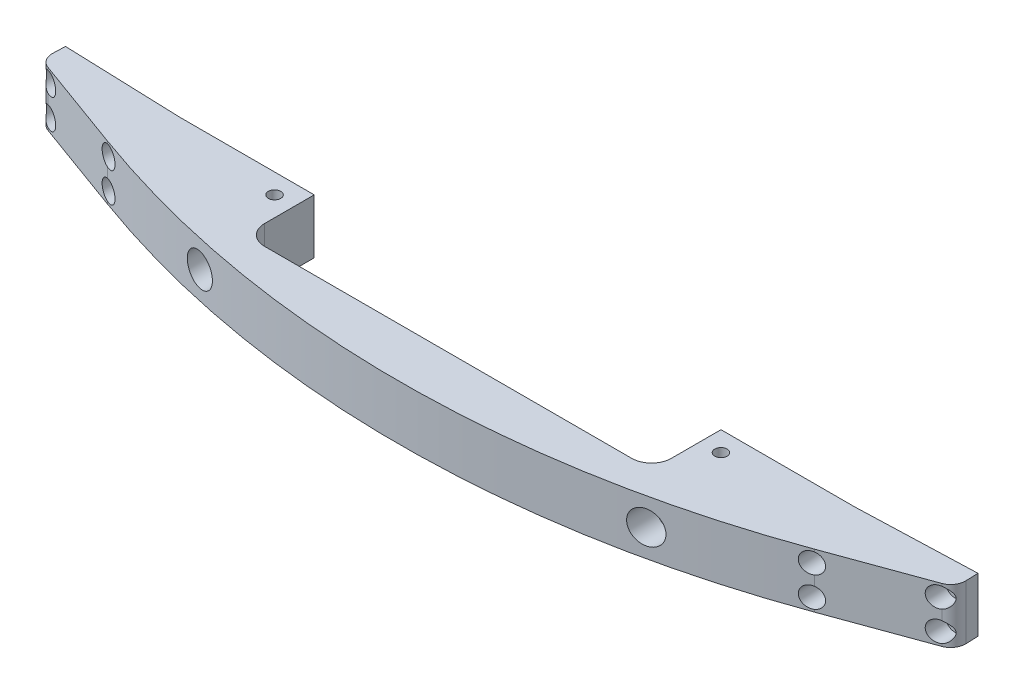
SolidWorks part; units mm, degrees
material "2014-T6"
ref_plane "Ebene vorne" through (0, 0, 0) normal (0, 0, 1) x (1, 0, 0)
ref_plane "Ebene oben" through (0, 0, 0) normal (0, 1, 0) x (1, 0, 0)
ref_plane "Ebene rechts" through (0, 0, 0) normal (1, 0, 0) x (0, 0, -1)
sketch "Skizze1" plane through (0, 0, 0) normal (0, 1, 0) x (1, 0, 0)
  line L0 (0, 87.9519) -> (0, -34.7709) construction
  line L1 (80, 0) -> (-80, 0) construction
  line L2 (-80, 4) -> (-45, 4)
  line L3 (-81.3681, -3.7588) -> (-71.2753, -7.4322)
  line L4 (0, -20) -> (0, -10)
  line L5 (-41, -10) -> (0, -10)
  line L6 (-41, 4) -> (-41, -10)
  line L7 (-80, 4) -> (-91.9927, 4.4188)
  line L8 (-45, 4) -> (-41, 4)
  line L9 (-92.1413, 0.1624) -> (-91.9781, 4.8376)
  line L10 (-92.1413, 0.1624) -> (-81.3681, -3.7588)
  line L11 (-91.9781, 4.8376) -> (-67.9927, 4)
  line L12 (-80, 4) -> (-79.9854, 4.4188) construction
  arc A0 (-80, 4) -> (-81.3681, -3.7588) centre (-80, 0) ccw construction
  arc A1 (-71.2753, -7.4322) -> (0, -20) centre (0, 188.395) ccw
  dimension "D2" = 160
  dimension "D9" = 20
  dimension "D3" = 8
  dimension "D7" = 2
  dimension "D1" = 12
  dimension "D4" = 90
  dimension "D5" = 20
  dimension "D6" = 4
  dimension "D8" = 10
extrude "Aufsatz-Linear austragen1" add sketch "Skizze1" along normal mid plane 11 contours A0 | L3 A1 L4 L5 L6 A0 | L7 L12 L11 L9 | L12 L2 L11 region at (-82.6569, 0, -4.3257) region at (-46.1863, 0, 7.1587)
fillet "Verrundung1" radius 4 1 edges at (-41, 0, 10)
hole_wizard "M3 Gewindebohrung1" positions "Skizze6" profile "Skizze5" tap size "M3" standard "DIN" end condition through all
sketch "Skizze6" plane through (-37.6887, 5.5, 8.4808) normal (0, 1, 0) x (1, 0, 0)
  line L0 (-7.3113, 8.4808) -> (-3.3113, 8.4808) construction
  line L3 (-7.3113, 12.4808) -> (-7.3113, 8.4808) construction
  line L5 (-3.3113, 12.4808) -> (-3.3113, 2.4808) construction
  line L6 (-30.3039, 12.4808) -> (-3.3113, 12.4808) construction
  line L7 (-3.3113, 8.4808) -> (37.6887, 8.4808) construction
  point P0 (-7.3113, 8.4808)
  dimension "D1" = 4
cosmetic thread "Bohrungsgewinde1"
sketch "Skizze5" plane through (-45, 5.5, 0) normal (1, 0, 0) x (0, 0, 1)
  line L0 (0, 0) -> (0, 11)
  line L1 (0, 11) -> (1.25, 11)
  line L2 (1.25, 11) -> (1.25, 0)
  line L5 (1.25, 0) -> (0, 0)
  line L11 (0, -6.35) -> (0, 107.95) construction
  dimension "Bohrerdurchmesser" = 2.5
  dimension "Bohrungstiefe" = 11
fillet "Verrundung2" radius 3 1 edges at (-92.1413, 0, -0.1624)
sketch "Skizze7" plane through (0.0567, 0, -1.6237) normal (0.0349, 0, -0.9994) x (-0.9994, 0, -0.0349)
  line L15 (70.5909, 3) -> (70.5909, -3) construction
  line L16 (70.5909, 0) -> (89.5909, 0) construction
  line L17 (89.5909, 3) -> (89.5909, -3) construction
  line L18 (89.5909, 0) -> (92.0909, 0) construction
  line L19 (92.0909, 5.5) -> (92.0909, -5.5) construction
  line L20 (68.0909, 0) -> (70.5909, 0) construction
  line L21 (68.0909, 5.5) -> (68.0909, -5.5) construction
  circle A0 centre (70.5909, 3) radius 2.05
  circle A1 centre (89.5909, 3) radius 2.05
  circle A2 centre (89.5909, -3) radius 2.05
  circle A3 centre (70.5909, -3) radius 2.05
  circle A4 centre (70.5909, -3) radius 1
  circle A5 centre (89.5909, -3) radius 1
  circle A6 centre (89.5909, 3) radius 1
  circle A7 centre (70.5909, 3) radius 1
  dimension "D1" = 2
  dimension "D3" = 4.1
  dimension "D2" = 6
  dimension "D4" = 19
extrude "Schnitt-Linear austragen1" cut sketch "Skizze7" against normal through all from offset 2 contours A0 | A3 | A1 | A2 offset against normal yes
extrude "Schnitt-Linear austragen2" cut sketch "Skizze7<3>" against normal through all contours A7 | A4 | A5 | A6
sketch "Skizze7<3>" plane through (0.0567, 0, -1.6237) normal (0.0349, 0, -0.9994) x (-0.9994, 0, -0.0349) same geometry as "Skizze7"
mirror "Spiegeln3" about plane through (0, 0, 0) normal (1, 0, 0) of bodies 111 101
ref_plane "Ebene1" through (0, 0, 20) normal (0, 0, 1) x (1, 0, 0)
hole_wizard "Stirnsenkung für  M3 Zylinderschraube mit Schlitz/Kreuzschlitz1" positions "Skizze4" profile "Skizze3" counterbore size "M3" standard "DIN" end condition through all
sketch "Skizze4" plane through (0, 0, 20) normal (0, 0, 1) x (1, 0, 0)
  line L0 (-45, 0) -> (45, 0) construction
  line L2 (-41, 5.5) -> (-41, -5.5) construction
  point P0 (-45, 0)
  point P2 (45, 0)
  dimension "D1" = 4
sketch "Skizze3" plane through (-45, 0, 20) normal (1, 0, 0) x (0, -1, 0)
  line L0 (0, 0) -> (0, 24.8376)
  line L1 (0, 24.8376) -> (1.6, 24.8376)
  line L3 (1.6, 24.8376) -> (1.6, 10)
  line L4 (1.6, 10) -> (3.25, 10)
  line L5 (3.25, 10) -> (3.25, 0)
  line L7 (3.25, 0) -> (0, 0)
  line L11 (0, -6.35) -> (0, 107.95) construction
  dimension "Bohrerdurchmesser" = 3.2
  dimension "Bohrungstiefe" = 24.8376
  dimension "Senkdurchmesser2" = 6.5
  dimension "Senktiefe2" = 10
